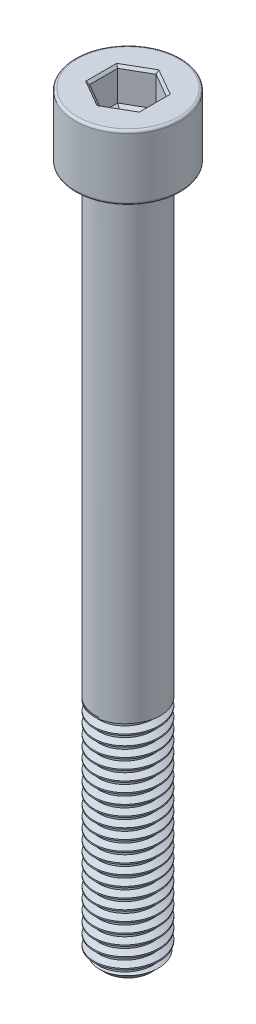
SolidWorks part; units mm, degrees
material "AISI Type A2 Tool Steel"
ref_plane "Front Plane" through (0, 0, 0) normal (0, 0, 1) x (1, 0, 0)
ref_plane "Top Plane" through (0, 0, 0) normal (0, 1, 0) x (1, 0, 0)
ref_plane "Right Plane" through (0, 0, 0) normal (1, 0, 0) x (0, 0, -1)
sketch "Sketch1" plane through (0, 0, 0) normal (0, 1, 0) x (1, 0, 0)
  circle A0 centre (0, 0) radius 4
  dimension "D1" = 8
extrude "Boss-Extrude1" add sketch "Sketch1" along normal blind 28
thread "Thread1" pitch 1.25 method cut profile "Thread Profile1" start angle 0, offset 2, length 0, pitch 1.25, diameter 8
ref_plane "Plane1" through (-4, 30, 0) normal (0, 0, 1) x (-1, 0, 0)
sketch "Thread Profile1" plane through (-4, 30, 0) normal (0, 0, 1) x (-1, 0, 0)
  line L0 (0, 0) -> (0, 1.25) construction
  line L11 (0, 0) -> (0, 1.0937)
  line L12 (0, 1.0937) -> (-0.6766, 0.7031)
  line L13 (-0.6766, 0.7031) -> (-0.6766, 0.3906)
  line L15 (-0.6766, 0.3906) -> (0, 0)
  line L17 (-0.6766, 0.5469) -> (0, 0.5469) construction
  point P2 (0, 0)
  dimension "Pitch" = 1.25
  dimension "Profile_Angle" = 60
  dimension "Profile_Land" = 0.3125
  dimension "Profile_Height" = 0.6766
sketch "Sketch2" plane through (0, 28, 0) normal (0, 1, 0) x (1, 0, 0)
  circle A0 centre (0, 0) radius 4
  dimension "D1" = 8
extrude "Boss-Extrude2" add sketch "Sketch2" along normal blind 57
sketch "Sketch5" plane through (0, 85, 0) normal (0, 1, 0) x (1, 0, 0)
  circle A0 centre (0, 0) radius 6.5
  dimension "D1" = 13
extrude "Boss-Extrude3" add sketch "Sketch5" along normal blind 8
sketch "Sketch6" plane through (0, 0, 0) normal (0, 0, 1) x (1, 0, 0)
  line L0 (0, 0) -> (0, 0.7245) construction
  line L1 (0, 0) -> (4.01, 0) construction
  line L2 (4.01, 0) -> (4.01, 1.2)
  line L3 (4.01, 1.2) -> (2.81, 0)
  line L4 (2.81, 0) -> (4.01, 0)
  dimension "D1" = 1.2
  dimension "D2" = 45
  dimension "D3" = 4.01
revolve "Cut-Revolve1" cut sketch "Sketch6" angle 360 about L0
fillet "Fillet1" radius 0.3 2 edges at (0, 85, 6.5) (0, 93, 6.5)
sketch "Sketch7" plane through (0, 93, 0) normal (0, 1, 0) x (1, 0, 0)
  line L1 (0, 3.4641) -> (-3, 1.7321)
  line L2 (-3, 1.7321) -> (-3, -1.7321)
  line L3 (-3, -1.7321) -> (0, -3.4641)
  line L4 (0, -3.4641) -> (3, -1.7321)
  line L5 (3, -1.7321) -> (3, 1.7321)
  line L6 (3, 1.7321) -> (0, 3.4641)
  circle A0 centre (0, 0) radius 3 construction
  dimension "D1" = 6
extrude "Cut-Extrude1" cut sketch "Sketch7" against normal blind 4
chamfer "Chamfer1" distance 0.3 angle 45 6 edges at (-3, 93, 0) (-1.5, 93, 2.5981) (1.5, 93, 2.5981) (3, 93, 0) (1.5, 93, -2.5981) (-1.5, 93, -2.5981)
sketch "Sketch8" plane through (0, 89, 0) normal (0, 1, 0) x (1, 0, 0)
  line L1 (0, 3.4641) -> (-3, 1.7321)
  line L2 (-3, 1.7321) -> (-3, -1.7321)
  line L3 (-3, -1.7321) -> (0, -3.4641)
  line L4 (0, -3.4641) -> (3, -1.7321)
  line L5 (3, -1.7321) -> (3, 1.7321)
  line L6 (3, 1.7321) -> (0, 3.4641)
  circle A0 centre (0, 0) radius 3 construction
extrude "Cut-Extrude2" cut sketch "Sketch8" against normal blind 0.4 draft 60
